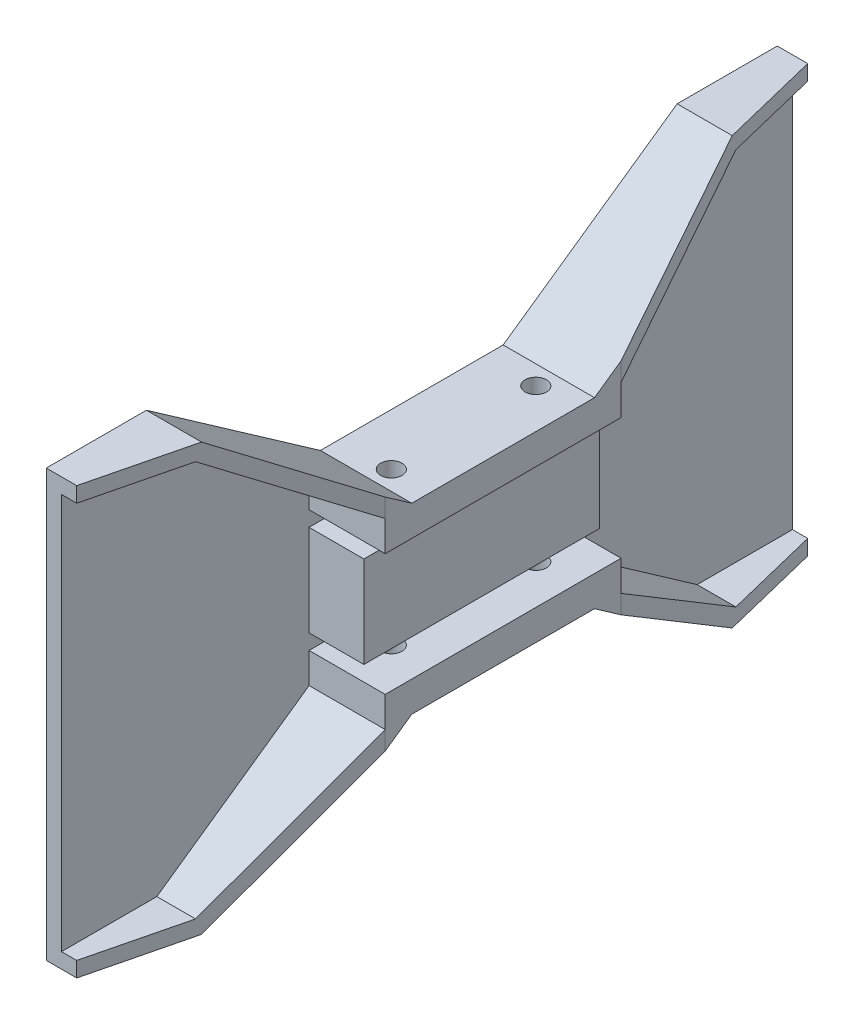
SolidWorks part; units mm, degrees
ref_plane "Front Plane" through (0, 0, 0) normal (1, 0, 0) x (0, 1, 0)
ref_plane "Top Plane" through (0, 0, 0) normal (0, 0, 1) x (0, 1, 0)
ref_plane "Right Plane" through (0, 0, 0) normal (0, 1, 0) x (-1, 0, 0)
sketch "Sketch1" plane through (0, 0, 0) normal (1, 0, 0) x (0, 1, 0)
  line L0 (-38.1, 0) -> (-38.1, -38.1)
  line L1 (0, 0) -> (-88.9, 0)
  line L2 (0, 0) -> (0, -152.4)
  line L3 (0, -152.4) -> (-88.9, -152.4)
  line L4 (-88.9, 0) -> (-88.9, -152.4)
  line L5 (-38.1, -38.1) -> (-88.9, -110.6499)
  line L6 (-82.55, -152.4) -> (-82.55, -112.6521)
  line L7 (-82.55, -112.6521) -> (-38.1, -49.1709)
  line L8 (-38.1, -49.1709) -> (-25.4, -49.1709)
  line L9 (-25.4, -49.1709) -> (-25.4, 0)
  line L10 (-19.05, 0) -> (-19.05, -49.1709)
  line L11 (-19.05, -49.1709) -> (0, -49.1709)
  point P16 (0, 0)
  dimension "D1" = 88.9
  dimension "D2" = 152.4
  dimension "D3" = 38.1
  dimension "D4" = 35
  dimension "D5" = 114.3
  dimension "D6" = 6.35
  dimension "D7" = 6.35
  dimension "D8" = 12.7
  dimension "D9" = 6.35
extrude "Boss-Extrude1" add sketch "Sketch1" against normal blind 6.35 contours L11 L10 L1 L9 L8 L7 L6 L3 L2 | L8 L9 L1 L0 L5 L4 L3 L6 L7 | L10 L11 L2 L1 region at (0, -52.9449, -64.1013) region at (0, -35.4448, -103.3686) region at (0, -9.525, -24.5854)
extrude "Boss-Extrude2" add sketch "Sketch1<4>" along normal blind 38.1 from surface contours L8 L9 L1 L0 L5 L4 L3 L6 L7 | L10 L11 L2 L1 region at (0, -52.9449, -64.1013) region at (0, -9.525, -24.5854) starting at face at (-6.35, -42.3333, -75.5917)
sketch "Sketch1<4>" plane through (0, 0, 0) normal (1, 0, 0) x (0, 1, 0) same geometry as "Sketch1"
extrude "Cut-Extrude1" cut sketch "Sketch1<6>" against normal blind 8.89 from surface contours L10 L11 L2 L1 region at (0, -9.525, -24.5854) starting at face at (31.75, -9.525, -24.5854)
sketch "Sketch1<6>" plane through (0, 0, 0) normal (1, 0, 0) x (0, 1, 0) same geometry as "Sketch1"
sketch "Sketch3" plane through (0, 0, 0) normal (0, 1, 0) x (-1, 0, 0)
  line L0 (-31.75, -49.1709) -> (0, -49.1709) construction
  line L1 (0, -112.6521) -> (0, -152.4) construction
  line L2 (0, -49.1709) -> (0, -112.6521) construction
  line L3 (-31.75, -152.4) -> (0, -152.4) construction
  line L4 (-31.75, -112.6521) -> (0, -112.6521) construction
  line L5 (-31.75, -152.4) -> (-31.75, -112.6521) construction
  line L6 (-31.75, -112.6521) -> (-31.75, -49.1709) construction
  line L7 (-31.75, -49.1709) -> (0, -49.1709)
  line L8 (0, -112.6521) -> (0, -152.4)
  line L9 (0, -49.1709) -> (0, -112.6521)
  line L10 (-31.75, -152.4) -> (0, -152.4)
  line L11 (-31.75, -112.6521) -> (0, -112.6521)
  line L12 (-31.75, -152.4) -> (-31.75, -112.6521)
  line L13 (-31.75, -112.6521) -> (-31.75, -49.1709)
  line L14 (-31.75, -49.1709) -> (-6.35, -152.4)
  line L15 (6.35, 0) -> (6.35, -152.4) construction
  circle A0 centre (-15.24, -30.1209) radius 4.445
  dimension "D2" = 8.89
  dimension "D1" = 12.7
  dimension "D3" = 19.05
  dimension "D4" = 21.59
extrude "Cut-Extrude2" cut sketch "Sketch3" against normal through all contours L14 L13 L11 | L14 L11 L12 L10 | A0 region at (26.5434, 0, -91.4917) region at (21.3007, 0, -134.1055) region at (15.24, 0, -30.1209)
mirror "Mirror1" about plane through (-6.35, 0, 0) normal (0, -1, 0) of bodies 104
mirror "Mirror2" about plane through (-6.35, 0, 0) normal (0, 0, 1) of bodies 105
